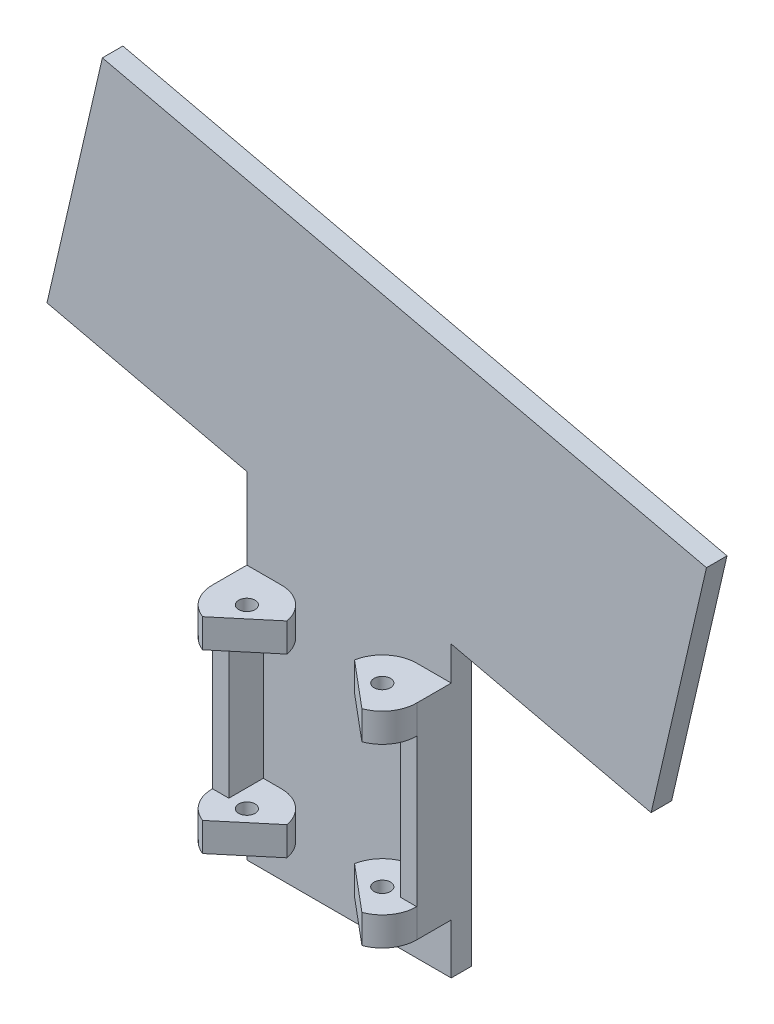
SolidWorks part; units mm, degrees
ref_plane "Front Plane" through (0, 0, 0) normal (0, 0, 1) x (1, 0, 0)
ref_plane "Top Plane" through (0, 0, 0) normal (0, 1, 0) x (1, 0, 0)
ref_plane "Right Plane" through (0, 0, 0) normal (1, 0, 0) x (0, 0, -1)
sketch "Sketch1" plane through (0, 0, 0) normal (0, 1, 0) x (1, 0, 0)
  line L0 (0, 22.8391) -> (0, -19.8342) construction
  line L1 (-35.1495, 0) -> (37.3645, 0) construction
  line L2 (-24.9, 0) -> (-24.9, 13.4)
  line L3 (-24.9, 13.4) -> (24.9, 13.4)
  line L4 (24.9, 0) -> (24.9, 13.4)
  line L5 (-19.4124, -7.879) -> (-8.235, 1.5)
  line L6 (19.4124, -7.879) -> (8.235, 1.5)
  line L7 (16.5, 8.4) -> (-16.5, 8.4)
  arc A0 (19.4124, -7.879) -> (24.9, 0) centre (16.5, 0) ccw
  arc A1 (-19.4124, -7.879) -> (-24.9, 0) centre (-16.5, 0) cw
  arc A2 (-16.5, 8.4) -> (-8.235, 1.5) centre (-16.5, 0) cw
  arc A3 (16.5, 8.4) -> (8.235, 1.5) centre (16.5, 0) ccw
  circle A4 centre (-16.5, 0) radius 8.4 construction
  circle A5 centre (16.5, 0) radius 8.4 construction
  point P14 (0, 13.4)
  dimension "D1" = 16.8
  dimension "D2" = 33
  dimension "D3" = 5
  dimension "D4" = 130
  dimension "D5" = 1.5
  dimension "D6" = 13.4
extrude "Boss-Extrude2" add sketch "Sketch1" along normal blind 7
sketch "Sketch3" plane through (0, 7, 0) normal (0, 1, 0) x (1, 0, 0)
  circle A0 centre (-16.5, 0) radius 2
  circle A1 centre (16.5, 0) radius 2
  dimension "D1" = 4
extrude "Cut-Extrude2" cut sketch "Sketch3" against normal through all both and the other way through all
sketch "Sketch4" plane through (0, 7, 0) normal (0, 1, 0) x (1, 0, 0)
  line L0 (-24.9, 13.4) -> (-24.9, 0)
  line L1 (-24.9, 13.4) -> (24.9, 13.4)
  line L2 (24.9, 13.4) -> (24.9, 0)
  line L3 (0, 13.4) -> (0, 0) construction
  line L4 (-16.5, 8.4) -> (16.5, 8.4)
  line L5 (-16.5, 8.4) -> (16.5, 8.4) construction
  line L6 (16.5, 8.4) -> (20.9, 8.4)
  line L7 (20.9, 8.4) -> (20.9, 0)
  line L8 (20.9, 0) -> (24.9, 0)
  line L9 (-20.9, 0) -> (-24.9, 0)
  line L10 (-20.9, 8.4) -> (-20.9, 0)
  line L11 (-16.5, 8.4) -> (-20.9, 8.4)
  circle A0 centre (-16.5, 0) radius 3.7 construction
  point P21 (0, 8.4)
  dimension "D2" = 7.4
  dimension "D1" = 4
extrude "Boss-Extrude3" add sketch "Sketch4" along normal blind 36
sketch "Sketch5" plane through (0, 43, 0) normal (0, 1, 0) x (1, 0, 0)
  line L12 (-24.9, 13.4) -> (-24.9, 0)
  line L13 (24.9, 13.4) -> (-24.9, 13.4)
  line L14 (24.9, 0) -> (24.9, 13.4)
  line L15 (8.235, 1.5) -> (19.4124, -7.879)
  line L16 (-16.5, 8.4) -> (16.5, 8.4)
  line L17 (-19.4124, -7.879) -> (-8.235, 1.5)
  line L18 (-24.9, 13.4) -> (-24.9, 0)
  line L19 (24.9, 13.4) -> (-24.9, 13.4)
  line L20 (24.9, 0) -> (24.9, 13.4)
  line L21 (8.235, 1.5) -> (19.4124, -7.879)
  line L22 (-16.5, 8.4) -> (16.5, 8.4)
  line L23 (-19.4124, -7.879) -> (-8.235, 1.5)
  circle A0 centre (-16.5, 0) radius 2 construction
  circle A1 centre (16.5, 0) radius 2
  circle A2 centre (16.5, 0) radius 2 construction
  circle A4 centre (-16.5, 0) radius 2
  arc A8 (-24.9, 0) -> (-19.4124, -7.879) centre (-16.5, 0) ccw
  arc A9 (19.4124, -7.879) -> (24.9, 0) centre (16.5, 0) ccw
  arc A10 (16.5, 8.4) -> (8.235, 1.5) centre (16.5, 0) ccw
  arc A11 (-8.235, 1.5) -> (-16.5, 8.4) centre (-16.5, 0) ccw
  arc A12 (-24.9, 0) -> (-19.4124, -7.879) centre (-16.5, 0) ccw
  arc A13 (19.4124, -7.879) -> (24.9, 0) centre (16.5, 0) ccw
  arc A14 (16.5, 8.4) -> (8.235, 1.5) centre (16.5, 0) ccw
  arc A15 (-8.235, 1.5) -> (-16.5, 8.4) centre (-16.5, 0) ccw
  dimension "D1" = 0
extrude "Boss-Extrude4" add sketch "Sketch5" along normal blind 7
sketch "Sketch14" plane through (0, 50, 0) normal (0, 1, 0) x (1, 0, 0)
  line L0 (24.9, 0) -> (24.9, 13.4) construction
  line L1 (-24.9, 13.4) -> (24.9, 13.4)
  line L2 (-24.9, 13.4) -> (-24.9, 8.4)
  line L3 (-24.9, 8.4) -> (24.9, 8.4)
  line L4 (24.9, 13.4) -> (24.9, 8.4)
  line L5 (-16.5, 8.4) -> (16.5, 8.4) construction
extrude "Boss-Extrude7" add sketch "Sketch14" along normal blind 8.25
sketch "Sketch16" plane through (0, 0, 0) normal (0, -1, 0) x (1, 0, 0)
  line L0 (24.9, 0) -> (24.9, -13.4) construction
  line L1 (-24.9, -13.4) -> (24.9, -13.4)
  line L2 (-24.9, -13.4) -> (-24.9, -8.4)
  line L3 (-24.9, -8.4) -> (24.9, -8.4)
  line L4 (24.9, -13.4) -> (24.9, -8.4)
  line L5 (-16.5, -8.4) -> (16.5, -8.4) construction
extrude "Boss-Extrude8" add sketch "Sketch16" along normal blind 12.25
sketch "Sketch17" plane through (0, 0, -13.4) normal (0, 0, -1) x (-1, 0, 0)
  line L0 (24.9, 58.25) -> (-24.9, 58.25)
  line L4 (24.9, 69.7472) -> (24.9, 58.25)
  line L5 (-24.9, 58.25) -> (-73.6185, 47.0024)
  line L6 (-73.6185, 47.0024) -> (-87.1156, 105.4647)
  line L7 (-87.1156, 105.4647) -> (60.1214, 139.457)
  line L8 (60.1214, 139.457) -> (73.6185, 80.9948)
  line L9 (73.6185, 80.9948) -> (24.9, 69.7472)
  point P4 (0, 0)
  dimension "D1" = 13
  dimension "D2" = 60
  dimension "D3" = 50
  dimension "D4" = 50
extrude "Boss-Extrude9" add sketch "Sketch17" against normal blind 5
